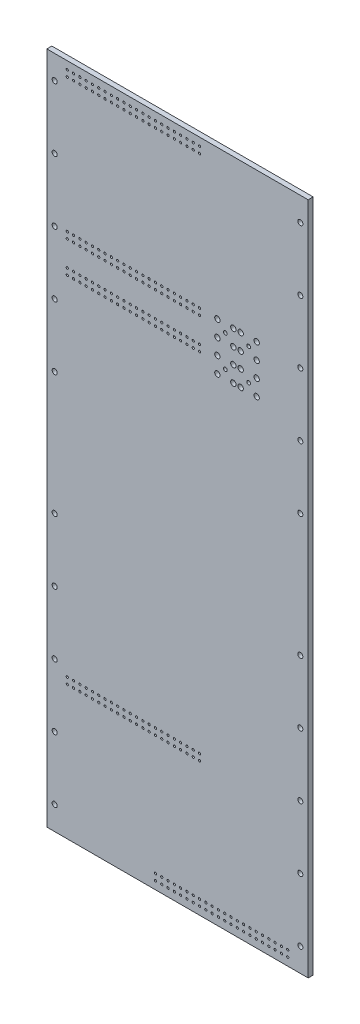
SolidWorks part; units mm, degrees
ref_plane "Front Plane" through (0, 0, 0) normal (0, 0, 1) x (1, 0, 0)
ref_plane "Top Plane" through (0, 0, 0) normal (0, 1, 0) x (1, 0, 0)
ref_plane "Right Plane" through (0, 0, 0) normal (1, 0, 0) x (0, 0, -1)
sketch "Sketch1" plane through (0, 0, 0) normal (0, 0, 1) x (1, 0, 0)
  line L1 (-41.5, -107) -> (41.5, -107)
  line L2 (-41.5, -107) -> (-41.5, 107)
  line L3 (-41.5, 107) -> (41.5, 107)
  line L4 (41.5, -107) -> (41.5, 107)
  line L5 (-41.5, -107) -> (41.5, 107) construction
  line L6 (-41.5, 107) -> (41.5, -107) construction
  point P0 (0, 0)
  dimension "D1" = 83
  dimension "D2" = 214
extrude "Boss-Extrude1" add sketch "Sketch1" along normal blind 1.5875
hole_wizard "#0 Clearance Hole1" positions "Sketch5" profile "Sketch3" hole size "#0" standard "ANSI Inch"
sketch "Sketch5" plane through (0, 0, 1.5875) normal (0, 0, 1) x (1, 0, 0)
  line L0 (0, 0) -> (0, 107) construction
  line L1 (41.5, 107) -> (-41.5, 107) construction
  line L4 (-41.5, 107) -> (-41.5, -107) construction
  line L5 (-41.5, 0) -> (41.5, 0) construction
  line L6 (41.5, -107) -> (41.5, 107) construction
  line L8 (-41.5, 7) -> (41.5, 7) construction
  line L9 (-41.5, 7) -> (-41.5, 107) construction
  line L10 (-41.5, 107) -> (41.5, 107) construction
  line L11 (41.5, 7) -> (41.5, 107) construction
  line L12 (-41.5, -107) -> (41.5, -107) construction
  point P490 (-39, 99.5)
  point P557 (39, 99.5)
  point P558 (39, 79.5)
  point P559 (39, 59.5)
  point P560 (39, 39.5)
  point P561 (39, 19.5)
  point P563 (-39, 79.5)
  point P564 (-39, 59.5)
  point P565 (-39, 39.5)
  point P566 (-39, 19.5)
  point P727 (-39, -19.5)
  point P728 (-39, -39.5)
  point P729 (-39, -59.5)
  point P730 (-39, -79.5)
  point P731 (39, -19.5)
  point P732 (39, -39.5)
  point P733 (39, -59.5)
  point P734 (39, -79.5)
  point P735 (39, -99.5)
  point P736 (-39, -99.5)
  dimension "D1" = 2.5
  dimension "D2" = 5
  dimension "D4" = 2.5
  dimension "D3" = 2
  dimension "D5" = 100
  dimension "D6" = 7.5
  dimension "D7" = 20
sketch "Sketch3" plane through (-39, 99.5, 1.5875) normal (1, 0, 0) x (0, -1, 0)
  line L0 (0, 0) -> (0, 3.6596)
  line L1 (0, 3.6596) -> (0.8064, 3.175)
  line L2 (0.8064, 3.175) -> (0.8064, 0)
  line L5 (0.8064, 0) -> (0, 0)
  line L10 (0, 3.6596) -> (-0.8065, 3.175) construction
  line L11 (0, -6.35) -> (0, 107.95) construction
  dimension "Hole Dia." = 1.6129
  dimension "Hole Depth" = 3.175
  dimension "Drill Angle" = 118
sketch "Sketch6" plane through (0, 0, 0) normal (0, 0, -1) x (-1, 0, 0)
  line L0 (41.5, -7) -> (-41.5, -7) construction
  line L1 (-36.2, 0) -> (36.3, 0)
  line L2 (-36.2, 0) -> (-36.2, -7)
  line L3 (-36.2, -7) -> (36.3, -7)
  line L4 (36.3, 0) -> (36.3, -7)
  dimension "D1" = 72.5
extrude "Boss-Extrude3" add sketch "Sketch6" along normal blind 4.9125
sketch "Sketch7" plane through (0, 0, 1.5875) normal (0, 0, 1) x (1, 0, 0)
  line L0 (0, 107) -> (0, -107) construction
  line L1 (41.5, 107) -> (-41.5, 107) construction
  line L2 (-41.5, -107) -> (41.5, -107) construction
  line L3 (-36, 61) -> (8, 61) construction
  line L4 (-36, 105.5) -> (8, 105.5) construction
  line L5 (-36, 105.5) -> (-36, 101.5) construction
  line L6 (-36, 101.5) -> (8, 101.5) construction
  line L7 (8, 105.5) -> (8, 101.5) construction
  line L8 (-36, 61) -> (-36, 57) construction
  line L9 (-36, 57) -> (8, 57) construction
  line L10 (8, 61) -> (8, 57) construction
  line L11 (-36, 59) -> (41.5, 59) construction
  line L12 (41.5, -107) -> (41.5, 107) construction
  line L13 (-36, -61.5) -> (8, -61.5) construction
  line L14 (11.7, 60.74) -> (18.7, 60.74) construction
  line L15 (11.7, 60.74) -> (11.7, 53.74) construction
  line L16 (11.7, 53.74) -> (18.7, 53.74) construction
  line L17 (18.7, 60.74) -> (18.7, 53.74) construction
  line L18 (-36, -61.5) -> (-36, -65.5) construction
  line L19 (-36, -65.5) -> (8, -65.5) construction
  line L20 (8, -61.5) -> (8, -65.5) construction
  line L21 (-8, -101.5) -> (36, -101.5) construction
  line L22 (-8, -101.5) -> (-8, -105.5) construction
  line L23 (-8, -105.5) -> (36, -105.5) construction
  line L24 (36, -101.5) -> (36, -105.5) construction
  line L25 (19.1, 60.74) -> (26.1, 60.74) construction
  line L26 (19.1, 60.74) -> (19.1, 53.74) construction
  line L27 (19.1, 53.74) -> (26.1, 53.74) construction
  line L28 (26.1, 60.74) -> (26.1, 53.74) construction
  line L29 (-36, 51) -> (8, 51) construction
  line L30 (-36, 51) -> (-36, 47) construction
  line L31 (-36, 47) -> (8, 47) construction
  line L32 (8, 51) -> (8, 47) construction
  line L33 (11.7, 50.74) -> (18.7, 50.74) construction
  line L34 (11.7, 50.74) -> (11.7, 43.74) construction
  line L35 (11.7, 43.74) -> (18.7, 43.74) construction
  line L36 (18.7, 50.74) -> (18.7, 43.74) construction
  line L37 (19.1, 50.74) -> (26.1, 50.74) construction
  line L38 (19.1, 50.74) -> (19.1, 43.74) construction
  line L39 (19.1, 43.74) -> (26.1, 43.74) construction
  line L40 (26.1, 50.74) -> (26.1, 43.74) construction
  line L41 (-36, 49) -> (41.5, 49) construction
  circle A0 centre (-35, 102.5) radius 0.35
  circle A1 centre (-33, 102.5) radius 0.35
  circle A2 centre (-31, 102.5) radius 0.35
  circle A3 centre (-29, 102.5) radius 0.35
  circle A4 centre (-27, 102.5) radius 0.35
  circle A5 centre (-25, 102.5) radius 0.35
  circle A6 centre (-23, 102.5) radius 0.35
  circle A7 centre (-21, 102.5) radius 0.35
  circle A8 centre (-19, 102.5) radius 0.35
  circle A9 centre (-17, 102.5) radius 0.35
  circle A10 centre (-15, 102.5) radius 0.35
  circle A11 centre (-13, 102.5) radius 0.35
  circle A12 centre (-11, 102.5) radius 0.35
  circle A13 centre (-9, 102.5) radius 0.35
  circle A14 centre (-7, 102.5) radius 0.35
  circle A15 centre (-5, 102.5) radius 0.35
  circle A16 centre (-3, 102.5) radius 0.35
  circle A17 centre (-1, 102.5) radius 0.35
  circle A18 centre (1, 102.5) radius 0.35
  circle A19 centre (3, 102.5) radius 0.35
  circle A20 centre (5, 102.5) radius 0.35
  circle A21 centre (7, 102.5) radius 0.35
  circle A22 centre (-33, 104.5) radius 0.35
  circle A23 centre (-31, 104.5) radius 0.35
  circle A24 centre (-29, 104.5) radius 0.35
  circle A25 centre (-27, 104.5) radius 0.35
  circle A26 centre (-25, 104.5) radius 0.35
  circle A27 centre (-23, 104.5) radius 0.35
  circle A28 centre (-21, 104.5) radius 0.35
  circle A29 centre (-19, 104.5) radius 0.35
  circle A30 centre (-17, 104.5) radius 0.35
  circle A31 centre (-15, 104.5) radius 0.35
  circle A32 centre (-13, 104.5) radius 0.35
  circle A33 centre (-11, 104.5) radius 0.35
  circle A34 centre (-9, 104.5) radius 0.35
  circle A35 centre (-7, 104.5) radius 0.35
  circle A36 centre (-5, 104.5) radius 0.35
  circle A37 centre (-3, 104.5) radius 0.35
  circle A38 centre (-1, 104.5) radius 0.35
  circle A39 centre (1, 104.5) radius 0.35
  circle A40 centre (3, 104.5) radius 0.35
  circle A41 centre (5, 104.5) radius 0.35
  circle A42 centre (7, 104.5) radius 0.35
  circle A43 centre (-35, 104.5) radius 0.35
  circle A44 centre (-35, 58) radius 0.35
  circle A45 centre (-33, 58) radius 0.35
  circle A46 centre (-31, 58) radius 0.35
  circle A47 centre (-29, 58) radius 0.35
  circle A48 centre (-27, 58) radius 0.35
  circle A49 centre (-25, 58) radius 0.35
  circle A50 centre (-23, 58) radius 0.35
  circle A51 centre (-21, 58) radius 0.35
  circle A52 centre (-19, 58) radius 0.35
  circle A53 centre (-17, 58) radius 0.35
  circle A54 centre (-15, 58) radius 0.35
  circle A55 centre (-13, 58) radius 0.35
  circle A56 centre (-11, 58) radius 0.35
  circle A57 centre (-9, 58) radius 0.35
  circle A58 centre (-7, 58) radius 0.35
  circle A59 centre (-5, 58) radius 0.35
  circle A60 centre (-3, 58) radius 0.35
  circle A61 centre (-1, 58) radius 0.35
  circle A62 centre (1, 58) radius 0.35
  circle A63 centre (3, 58) radius 0.35
  circle A64 centre (5, 58) radius 0.35
  circle A65 centre (7, 58) radius 0.35
  circle A66 centre (-33, 60) radius 0.35
  circle A67 centre (-31, 60) radius 0.35
  circle A68 centre (-29, 60) radius 0.35
  circle A69 centre (-27, 60) radius 0.35
  circle A70 centre (-25, 60) radius 0.35
  circle A71 centre (-23, 60) radius 0.35
  circle A72 centre (-21, 60) radius 0.35
  circle A73 centre (-19, 60) radius 0.35
  circle A74 centre (-17, 60) radius 0.35
  circle A75 centre (-15, 60) radius 0.35
  circle A76 centre (-13, 60) radius 0.35
  circle A77 centre (-11, 60) radius 0.35
  circle A78 centre (-9, 60) radius 0.35
  circle A79 centre (-7, 60) radius 0.35
  circle A80 centre (-5, 60) radius 0.35
  circle A81 centre (-3, 60) radius 0.35
  circle A82 centre (-1, 60) radius 0.35
  circle A83 centre (1, 60) radius 0.35
  circle A84 centre (3, 60) radius 0.35
  circle A85 centre (5, 60) radius 0.35
  circle A86 centre (7, 60) radius 0.35
  circle A87 centre (-35, 60) radius 0.35
  circle A88 centre (15.2, 57.24) radius 0.5842
  circle A89 centre (12.66, 59.78) radius 0.8509
  circle A90 centre (17.74, 59.78) radius 0.8509
  circle A91 centre (17.74, 54.7) radius 0.8509
  circle A92 centre (12.66, 54.7) radius 0.8509
  circle A93 centre (15.2, 57.24) radius 0.24 construction
  circle A94 centre (-35, -64.5) radius 0.35
  circle A95 centre (-33, -64.5) radius 0.35
  circle A96 centre (-31, -64.5) radius 0.35
  circle A97 centre (-29, -64.5) radius 0.35
  circle A98 centre (-27, -64.5) radius 0.35
  circle A99 centre (-25, -64.5) radius 0.35
  circle A100 centre (-23, -64.5) radius 0.35
  circle A101 centre (-21, -64.5) radius 0.35
  circle A102 centre (-19, -64.5) radius 0.35
  circle A103 centre (-17, -64.5) radius 0.35
  circle A104 centre (-15, -64.5) radius 0.35
  circle A105 centre (-13, -64.5) radius 0.35
  circle A106 centre (-11, -64.5) radius 0.35
  circle A107 centre (-9, -64.5) radius 0.35
  circle A108 centre (-7, -64.5) radius 0.35
  circle A109 centre (-5, -64.5) radius 0.35
  circle A110 centre (-3, -64.5) radius 0.35
  circle A111 centre (-1, -64.5) radius 0.35
  circle A112 centre (1, -64.5) radius 0.35
  circle A113 centre (3, -64.5) radius 0.35
  circle A114 centre (5, -64.5) radius 0.35
  circle A115 centre (7, -64.5) radius 0.35
  circle A116 centre (-33, -62.5) radius 0.35
  circle A117 centre (-31, -62.5) radius 0.35
  circle A118 centre (-29, -62.5) radius 0.35
  circle A119 centre (-27, -62.5) radius 0.35
  circle A120 centre (-25, -62.5) radius 0.35
  circle A121 centre (-23, -62.5) radius 0.35
  circle A122 centre (-21, -62.5) radius 0.35
  circle A123 centre (-19, -62.5) radius 0.35
  circle A124 centre (-17, -62.5) radius 0.35
  circle A125 centre (-15, -62.5) radius 0.35
  circle A126 centre (-13, -62.5) radius 0.35
  circle A127 centre (-11, -62.5) radius 0.35
  circle A128 centre (-9, -62.5) radius 0.35
  circle A129 centre (-7, -62.5) radius 0.35
  circle A130 centre (-5, -62.5) radius 0.35
  circle A131 centre (-3, -62.5) radius 0.35
  circle A132 centre (-1, -62.5) radius 0.35
  circle A133 centre (1, -62.5) radius 0.35
  circle A134 centre (3, -62.5) radius 0.35
  circle A135 centre (5, -62.5) radius 0.35
  circle A136 centre (7, -62.5) radius 0.35
  circle A137 centre (-35, -62.5) radius 0.35
  circle A138 centre (-7, -104.5) radius 0.35
  circle A139 centre (-5, -104.5) radius 0.35
  circle A140 centre (-3, -104.5) radius 0.35
  circle A141 centre (-1, -104.5) radius 0.35
  circle A142 centre (1, -104.5) radius 0.35
  circle A143 centre (3, -104.5) radius 0.35
  circle A144 centre (5, -104.5) radius 0.35
  circle A145 centre (7, -104.5) radius 0.35
  circle A146 centre (9, -104.5) radius 0.35
  circle A147 centre (11, -104.5) radius 0.35
  circle A148 centre (13, -104.5) radius 0.35
  circle A149 centre (15, -104.5) radius 0.35
  circle A150 centre (17, -104.5) radius 0.35
  circle A151 centre (19, -104.5) radius 0.35
  circle A152 centre (21, -104.5) radius 0.35
  circle A153 centre (23, -104.5) radius 0.35
  circle A154 centre (25, -104.5) radius 0.35
  circle A155 centre (27, -104.5) radius 0.35
  circle A156 centre (29, -104.5) radius 0.35
  circle A157 centre (31, -104.5) radius 0.35
  circle A158 centre (33, -104.5) radius 0.35
  circle A159 centre (35, -104.5) radius 0.35
  circle A160 centre (-5, -102.5) radius 0.35
  circle A161 centre (-3, -102.5) radius 0.35
  circle A162 centre (-1, -102.5) radius 0.35
  circle A163 centre (1, -102.5) radius 0.35
  circle A164 centre (3, -102.5) radius 0.35
  circle A165 centre (5, -102.5) radius 0.35
  circle A166 centre (7, -102.5) radius 0.35
  circle A167 centre (9, -102.5) radius 0.35
  circle A168 centre (11, -102.5) radius 0.35
  circle A169 centre (13, -102.5) radius 0.35
  circle A170 centre (15, -102.5) radius 0.35
  circle A171 centre (17, -102.5) radius 0.35
  circle A172 centre (19, -102.5) radius 0.35
  circle A173 centre (21, -102.5) radius 0.35
  circle A174 centre (23, -102.5) radius 0.35
  circle A175 centre (25, -102.5) radius 0.35
  circle A176 centre (27, -102.5) radius 0.35
  circle A177 centre (29, -102.5) radius 0.35
  circle A178 centre (31, -102.5) radius 0.35
  circle A179 centre (33, -102.5) radius 0.35
  circle A180 centre (35, -102.5) radius 0.35
  circle A181 centre (-7, -102.5) radius 0.35
  circle A182 centre (22.6, 57.24) radius 0.5842
  circle A183 centre (20.06, 59.78) radius 0.8509
  circle A184 centre (25.14, 59.78) radius 0.8509
  circle A185 centre (25.14, 54.7) radius 0.8509
  circle A186 centre (20.06, 54.7) radius 0.8509
  circle A187 centre (22.6, 57.24) radius 0.24 construction
  circle A188 centre (-35, 48) radius 0.35
  circle A189 centre (-33, 48) radius 0.35
  circle A190 centre (-31, 48) radius 0.35
  circle A191 centre (-29, 48) radius 0.35
  circle A192 centre (-27, 48) radius 0.35
  circle A193 centre (-25, 48) radius 0.35
  circle A194 centre (-23, 48) radius 0.35
  circle A195 centre (-21, 48) radius 0.35
  circle A196 centre (-19, 48) radius 0.35
  circle A197 centre (-17, 48) radius 0.35
  circle A198 centre (-15, 48) radius 0.35
  circle A199 centre (-13, 48) radius 0.35
  circle A200 centre (-11, 48) radius 0.35
  circle A201 centre (-9, 48) radius 0.35
  circle A202 centre (-7, 48) radius 0.35
  circle A203 centre (-5, 48) radius 0.35
  circle A204 centre (-3, 48) radius 0.35
  circle A205 centre (-1, 48) radius 0.35
  circle A206 centre (1, 48) radius 0.35
  circle A207 centre (3, 48) radius 0.35
  circle A208 centre (5, 48) radius 0.35
  circle A209 centre (7, 48) radius 0.35
  circle A210 centre (-33, 50) radius 0.35
  circle A211 centre (-31, 50) radius 0.35
  circle A212 centre (-29, 50) radius 0.35
  circle A213 centre (-27, 50) radius 0.35
  circle A214 centre (-25, 50) radius 0.35
  circle A215 centre (-23, 50) radius 0.35
  circle A216 centre (-21, 50) radius 0.35
  circle A217 centre (-19, 50) radius 0.35
  circle A218 centre (-17, 50) radius 0.35
  circle A219 centre (-15, 50) radius 0.35
  circle A220 centre (-13, 50) radius 0.35
  circle A221 centre (-11, 50) radius 0.35
  circle A222 centre (-9, 50) radius 0.35
  circle A223 centre (-7, 50) radius 0.35
  circle A224 centre (-5, 50) radius 0.35
  circle A225 centre (-3, 50) radius 0.35
  circle A226 centre (-1, 50) radius 0.35
  circle A227 centre (1, 50) radius 0.35
  circle A228 centre (3, 50) radius 0.35
  circle A229 centre (5, 50) radius 0.35
  circle A230 centre (7, 50) radius 0.35
  circle A231 centre (-35, 50) radius 0.35
  circle A232 centre (15.2, 47.24) radius 0.5842
  circle A233 centre (12.66, 49.78) radius 0.8509
  circle A234 centre (17.74, 49.78) radius 0.8509
  circle A235 centre (17.74, 44.7) radius 0.8509
  circle A236 centre (12.66, 44.7) radius 0.8509
  circle A237 centre (22.6, 47.24) radius 0.5842
  circle A238 centre (20.06, 49.78) radius 0.8509
  circle A239 centre (25.14, 49.78) radius 0.8509
  circle A240 centre (25.14, 44.7) radius 0.8509
  circle A241 centre (20.06, 44.7) radius 0.8509
  circle A242 centre (15.2, 47.24) radius 0.24 construction
  circle A243 centre (22.6, 47.24) radius 0.24 construction
  dimension "D1" = 0.7
  dimension "D14" = 1.1684
  dimension "D15" = 1.7018
  dimension "D27" = 0.48
  dimension "D4" = 2
  dimension "D5" = 42
  dimension "D6" = 1
  dimension "D7" = 1
  dimension "D8" = 4
  dimension "D9" = 44
  dimension "D10" = 15
  dimension "D11" = 2.5
  dimension "D12" = 2
  dimension "D13" = 7.2
  dimension "D16" = 2.54
  dimension "D17" = 2.54
  dimension "D20" = 5.08
  dimension "D21" = 5.08
  dimension "D22" = 7
  dimension "D23" = 3.5
  dimension "D24" = 3.5
  dimension "D25" = 50
  dimension "D26" = 2
  dimension "D29" = 7.4
  dimension "D30" = 40
  dimension "D32" = 2.5
  dimension "D33" = 1
  dimension "D35" = 10
  dimension "D2" = 22
  dimension "D3" = 2
  dimension "D18" = 2
  dimension "D19" = 2
  dimension "D28" = 2
  dimension "D31" = 2
  dimension "D34" = 2
extrude "Cut-Extrude1" cut sketch "Sketch7" against normal through all
sketch "Sketch8" plane through (0, 0, 1.5875) normal (0, 0, 1) x (1, 0, 0)
  line L0 (41.5, -107) -> (41.5, 107) construction
  line L3 (-41.5, 107) -> (41.5, 107)
  line L4 (-41.5, 107) -> (-41.5, 105.5)
  line L5 (-41.5, 105.5) -> (41.5, 105.5)
  line L6 (41.5, 107) -> (41.5, 105.5)
  line L7 (-41.5, 97) -> (41.5, 97)
  line L8 (-41.5, 97) -> (-41.5, 95.5)
  line L9 (-41.5, 95.5) -> (41.5, 95.5)
  line L10 (41.5, 97) -> (41.5, 95.5)
  line L11 (-41.5, 87) -> (41.5, 87)
  line L12 (-41.5, 87) -> (-41.5, 85.5)
  line L13 (-41.5, 85.5) -> (41.5, 85.5)
  line L14 (41.5, 87) -> (41.5, 85.5)
  line L15 (-41.5, 77) -> (41.5, 77)
  line L16 (-41.5, 77) -> (-41.5, 75.5)
  line L17 (-41.5, 75.5) -> (41.5, 75.5)
  line L18 (41.5, 77) -> (41.5, 75.5)
  line L19 (-41.5, 67) -> (41.5, 67)
  line L20 (-41.5, 67) -> (-41.5, 65.5)
  line L21 (-41.5, 65.5) -> (41.5, 65.5)
  line L22 (41.5, 67) -> (41.5, 65.5)
  line L23 (-41.5, 57) -> (41.5, 57)
  line L24 (-41.5, 57) -> (-41.5, 55.5)
  line L25 (-41.5, 55.5) -> (41.5, 55.5)
  line L26 (41.5, 57) -> (41.5, 55.5)
  line L27 (-41.5, 47) -> (41.5, 47)
  line L28 (-41.5, 47) -> (-41.5, 45.5)
  line L29 (-41.5, 45.5) -> (41.5, 45.5)
  line L30 (41.5, 47) -> (41.5, 45.5)
  line L31 (-41.5, 37) -> (41.5, 37)
  line L32 (-41.5, 37) -> (-41.5, 35.5)
  line L33 (-41.5, 35.5) -> (41.5, 35.5)
  line L34 (41.5, 37) -> (41.5, 35.5)
  line L35 (-41.5, 27) -> (41.5, 27)
  line L36 (-41.5, 27) -> (-41.5, 25.5)
  line L37 (-41.5, 25.5) -> (41.5, 25.5)
  line L38 (41.5, 27) -> (41.5, 25.5)
  line L39 (-41.5, 17) -> (41.5, 17)
  line L40 (-41.5, 17) -> (-41.5, 15.5)
  line L41 (-41.5, 15.5) -> (41.5, 15.5)
  line L42 (41.5, 17) -> (41.5, 15.5)
  line L43 (-41.5, 7) -> (41.5, 7)
  line L44 (-41.5, 7) -> (-41.5, 5.5)
  line L45 (-41.5, 5.5) -> (41.5, 5.5)
  line L46 (41.5, 7) -> (41.5, 5.5)
  line L47 (-41.5, 0) -> (41.5, 0) construction
  line L48 (-41.5, 107) -> (-41.5, -107) construction
  line L49 (41.5, -7) -> (41.5, -5.5)
  line L50 (-41.5, -5.5) -> (41.5, -5.5)
  line L51 (-41.5, -7) -> (-41.5, -5.5)
  line L52 (-41.5, -7) -> (41.5, -7)
  line L53 (41.5, -17) -> (41.5, -15.5)
  line L54 (-41.5, -15.5) -> (41.5, -15.5)
  line L55 (-41.5, -17) -> (-41.5, -15.5)
  line L56 (-41.5, -17) -> (41.5, -17)
  line L57 (41.5, -27) -> (41.5, -25.5)
  line L58 (-41.5, -25.5) -> (41.5, -25.5)
  line L59 (-41.5, -27) -> (-41.5, -25.5)
  line L60 (-41.5, -27) -> (41.5, -27)
  line L61 (41.5, -37) -> (41.5, -35.5)
  line L62 (-41.5, -35.5) -> (41.5, -35.5)
  line L63 (-41.5, -37) -> (-41.5, -35.5)
  line L64 (-41.5, -37) -> (41.5, -37)
  line L65 (41.5, -47) -> (41.5, -45.5)
  line L66 (-41.5, -45.5) -> (41.5, -45.5)
  line L67 (-41.5, -47) -> (-41.5, -45.5)
  line L68 (-41.5, -47) -> (41.5, -47)
  line L69 (41.5, -57) -> (41.5, -55.5)
  line L70 (-41.5, -55.5) -> (41.5, -55.5)
  line L71 (-41.5, -57) -> (-41.5, -55.5)
  line L72 (-41.5, -57) -> (41.5, -57)
  line L73 (41.5, -67) -> (41.5, -65.5)
  line L74 (-41.5, -65.5) -> (41.5, -65.5)
  line L75 (-41.5, -67) -> (-41.5, -65.5)
  line L76 (-41.5, -67) -> (41.5, -67)
  line L77 (41.5, -77) -> (41.5, -75.5)
  line L78 (-41.5, -75.5) -> (41.5, -75.5)
  line L79 (-41.5, -77) -> (-41.5, -75.5)
  line L80 (-41.5, -77) -> (41.5, -77)
  line L81 (41.5, -87) -> (41.5, -85.5)
  line L82 (-41.5, -85.5) -> (41.5, -85.5)
  line L83 (-41.5, -87) -> (-41.5, -85.5)
  line L84 (-41.5, -87) -> (41.5, -87)
  line L85 (41.5, -97) -> (41.5, -95.5)
  line L86 (-41.5, -95.5) -> (41.5, -95.5)
  line L87 (-41.5, -97) -> (-41.5, -95.5)
  line L88 (-41.5, -97) -> (41.5, -97)
  line L89 (41.5, -107) -> (41.5, -105.5)
  line L90 (-41.5, -105.5) -> (41.5, -105.5)
  line L91 (-41.5, -107) -> (-41.5, -105.5)
  line L92 (-41.5, -107) -> (41.5, -107)
  dimension "D1" = 1.5
  dimension "D3" = 10
  dimension "D2" = 11
